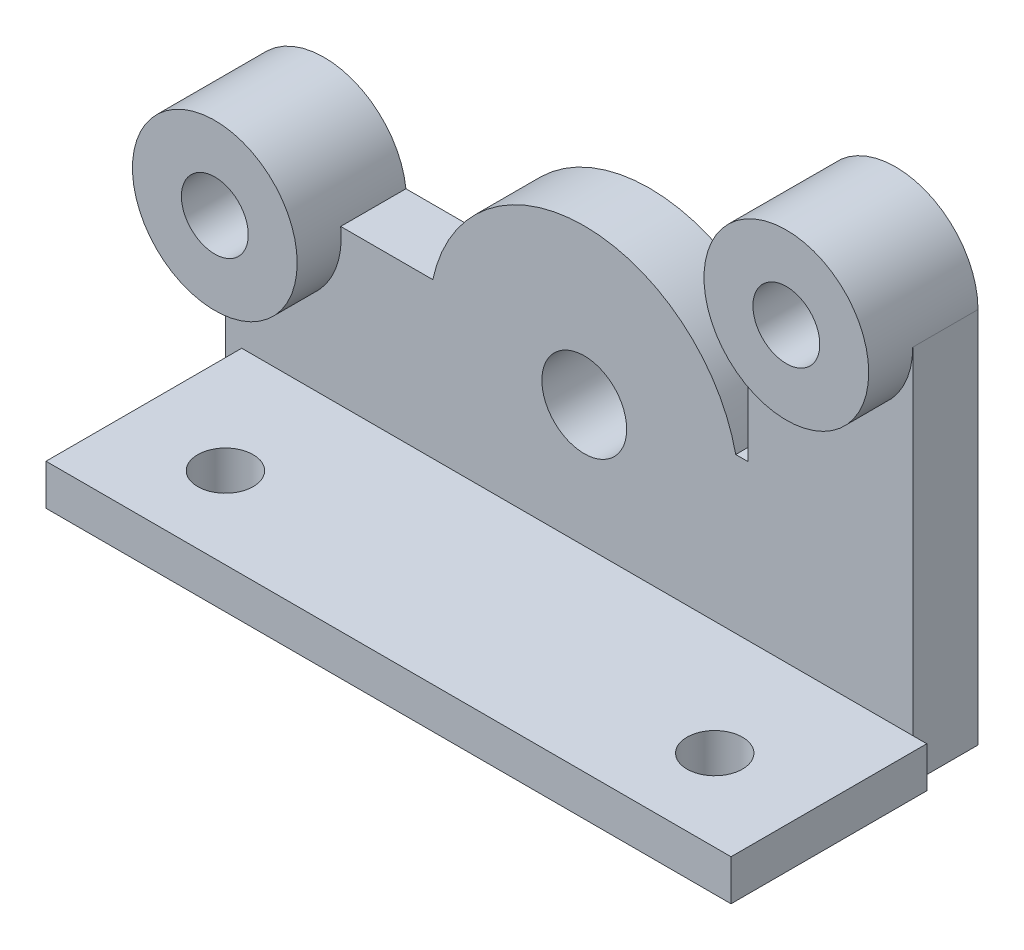
SolidWorks part; units mm, degrees
ref_plane "Front Plane" through (0, 0, 0) normal (0, 0, 1) x (1, 0, 0)
ref_plane "Top Plane" through (0, 0, 0) normal (0, 1, 0) x (1, 0, 0)
ref_plane "Right Plane" through (0, 0, 0) normal (1, 0, 0) x (0, 0, -1)
ref_plane "Plane1" through (0, 0, 358.5) normal (0, 0, 1) x (1, 0, 0)
sketch "Sketch1" plane through (0, 0, 358.5) normal (0, 0, 1) x (1, 0, 0)
  line L0 (278, 30) -> (319, 30)
  line L1 (319, 30) -> (319, 42)
  line L2 (319, 42) -> (278, 42)
  line L3 (278, 42) -> (278, 30)
extrude "Boss-Extrude1" add sketch "Sketch1" along normal blind 4
sketch "Sketch2" plane through (0, 0, 358.5) normal (0, 0, 1) x (1, 0, 0)
  circle A0 centre (300, 40) radius 9.5
  circle A1 centre (300, 40) radius 2.6
extrude "Boss-Extrude2" add sketch "Sketch2" along normal blind 4
sketch "Sketch3" plane through (0, 0, 358.5) normal (0, 0, 1) x (1, 0, 0)
  circle A0 centre (315.0909, 53.1249) radius 5.05
extrude "Boss-Extrude3" add sketch "Sketch3" along normal blind 4
sketch "Sketch4" plane through (0, 0, 358.5) normal (0, 0, 1) x (1, 0, 0)
  circle A0 centre (280.0506, 41.4224) radius 5.05
extrude "Boss-Extrude4" add sketch "Sketch4" along normal blind 4
sketch "Sketch5" plane through (0, 0, 358.5) normal (0, 0, 1) x (1, 0, 0)
  line L0 (310.0409, 30) -> (320.1409, 30)
  line L1 (320.1409, 30) -> (320.1409, 53.1249)
  line L2 (320.1409, 53.1249) -> (310.0409, 53.1249)
  line L3 (310.0409, 53.1249) -> (310.0409, 30)
extrude "Boss-Extrude5" add sketch "Sketch5" along normal blind 4
ref_plane "Plane2" through (0, 30, 0) normal (0, 1, 0) x (1, 0, 0)
sketch "Sketch6" plane through (0, 30, 0) normal (0, 1, 0) x (1, 0, 0)
  line L0 (279, -362.5) -> (321, -362.5)
  line L1 (321, -362.5) -> (321, -374.5)
  line L2 (321, -374.5) -> (279, -374.5)
  line L3 (279, -374.5) -> (279, -362.5)
  circle A0 centre (285, -369.5) radius 1.7
  circle A1 centre (315, -369.5) radius 1.7
extrude "Boss-Extrude6" add sketch "Sketch6" along normal blind 2.5
sketch "Sketch7" plane through (0, 0, 358.5) normal (0, 0, 1) x (1, 0, 0)
  circle A0 centre (300, 40) radius 2.6
extrude "Cut-Extrude1" cut sketch "Sketch7" along normal blind 4
ref_plane "Plane3" through (0, 0, 362.5) normal (0, 0, 1) x (1, 0, 0)
sketch "Sketch8" plane through (0, 0, 362.5) normal (0, 0, 1) x (1, 0, 0)
  circle A0 centre (315.0909, 53.1249) radius 5.05
  circle A1 centre (280.0506, 41.4224) radius 5.05
extrude "Boss-Extrude7" add sketch "Sketch8" along normal blind 2.7
sketch "Sketch9" plane through (0, 0, 358.5) normal (0, 0, 1) x (1, 0, 0)
  circle A0 centre (315.0909, 53.1249) radius 2.05
  circle A1 centre (280.0506, 41.4224) radius 2.05
extrude "Cut-Extrude2" cut sketch "Sketch9" along normal blind 6.7
ref_plane "Plane4" through (300, 0, 0) normal (1, 0, 0) x (0, 0, -1)
ref_plane "Plane5" through (0, 40, 0) normal (0, 1, 0) x (1, 0, 0)
ref_axis "ANKLE_AXIS" through (300, 40, 375.3) along (0, 0, -1)
